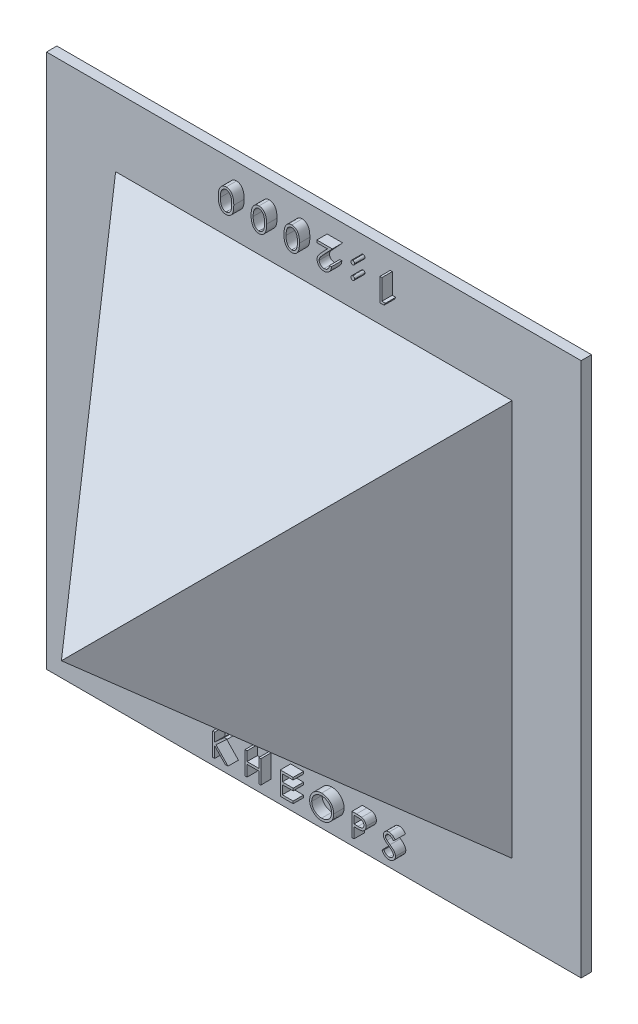
SolidWorks part; units mm, degrees
ref_plane "Plan de face" through (0, 0, 0) normal (0, 0, 1) x (1, 0, 0)
ref_plane "Plan de dessus" through (0, 0, 0) normal (0, 1, 0) x (1, 0, 0)
ref_plane "Plan de droite" through (0, 0, 0) normal (1, 0, 0) x (0, 0, -1)
sketch "Esquisse1" plane through (0, 0, 0) normal (0, 0, 1) x (1, 0, 0)
  line L1 (0, 0) -> (114.75, 0)
  line L2 (0, 0) -> (0, 114.75)
  line L3 (0, 114.75) -> (114.75, 114.75)
  line L4 (114.75, 0) -> (114.75, 114.75)
  dimension "D1" = 114.75
extrude "Boss.-Extru.1" add sketch "Esquisse1" along normal blind 97.7 draft 38.14
sketch "Esquisse3" plane through (0, 0, 0) normal (0, 0, -1) x (-1, 0, 0)
  line L8 (20, -20) -> (20, 134.75)
  line L9 (20, 134.75) -> (-134.75, 134.75)
  line L10 (-134.75, 134.75) -> (-134.75, -20)
  line L11 (-134.75, -20) -> (20, -20)
  line L12 (20, -20) -> (20, 134.75)
  line L13 (20, 134.75) -> (-134.75, 134.75)
  line L14 (-134.75, 134.75) -> (-134.75, -20)
  line L15 (-134.75, -20) -> (20, -20)
  dimension "D1" = 20
extrude "Boss.-Extru.3" add sketch "Esquisse3" along normal blind 3 separate body
sketch "Esquisse2" plane through (0, 0, -3) normal (0, 0, -1) x (-1, 0, 0)
  line L0 (0, 0) -> (-114.75, 0) construction
  line L1 (0, 114.75) -> (0, 0) construction
  circle A0 centre (-57.375, 57.375) radius 24
  point P5 (-57.375, 0)
  point P8 (0, 57.375)
  dimension "D1" = 48
extrude "Boss.-Extru.2" [suppressed] add sketch "Esquisse2" along normal blind 30
sketch "Esquisse4" plane through (0, 0, 0) normal (0, 0, 1) x (1, 0, 0)
  line L0 (30.2453, -15) -> (84.5047, -15) construction
  line L2 (134.75, -20) -> (-20, -20) construction
  line L3 (32.375, 129.75) -> (82.375, 129.75) construction
  line L6 (-20, 134.75) -> (134.75, 134.75) construction
  line L7 (114.75, 114.75) -> (0, 114.75) construction
  line L8 (0, 0) -> (114.75, 0) construction
  text T0 "KHEOPS" font "Century Gothic" height in points 25
  text T1 "1:2000\r\n" font "Century Gothic" height in points 25
  point P4 (57.375, 0)
  point P5 (57.375, -15)
  point P15 (57.375, 114.75)
  point P16 (57.375, 129.75)
  dimension "D1" = 5
  dimension "D2" = 5
  dimension "D3" = 50
extrude "Boss.-Extru.4" add sketch "Esquisse4" along normal blind 3
